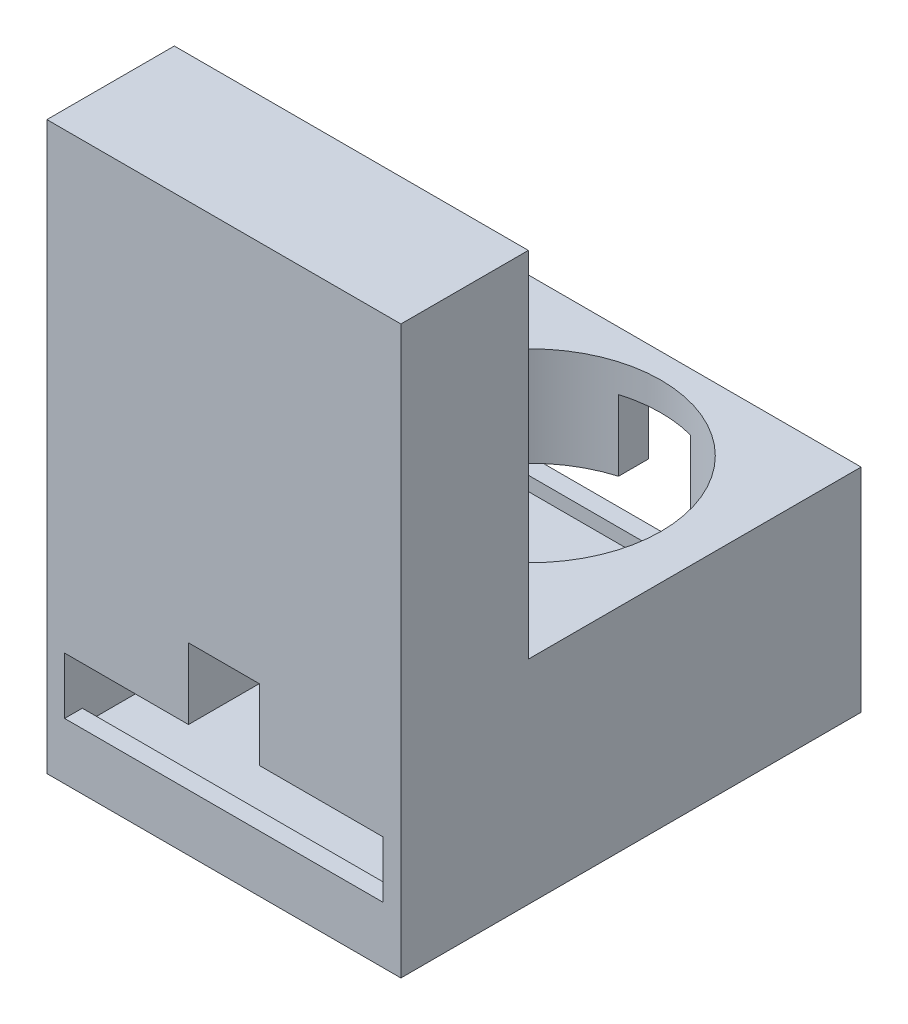
SolidWorks part; units mm, degrees
ref_plane "Front Plane" through (0, 0, 0) normal (0, 0, 1) x (1, 0, 0)
ref_plane "Top Plane" through (0, 0, 0) normal (0, 1, 0) x (1, 0, 0)
ref_plane "Right Plane" through (0, 0, 0) normal (1, 0, 0) x (0, 0, -1)
sketch "Sketch1" plane through (0, 0, 0) normal (0, 1, 0) x (1, 0, 0)
  line L1 (0, 0) -> (50, 0)
  line L2 (0, 0) -> (0, 65)
  line L3 (0, 65) -> (50, 65)
  line L4 (50, 0) -> (50, 65)
  dimension "D1" = 50
  dimension "D2" = 65
extrude "Boss-Extrude1" add sketch "Sketch1" along normal blind 30
sketch "Sketch3" plane through (0, 0, 0) normal (0, 0, 1) x (1, 0, 0)
  line L0 (0, 0) -> (50, 0) construction
  line L1 (2.5, 8) -> (47.5, 8)
  line L2 (2.5, 8) -> (2.5, 16)
  line L3 (2.5, 16) -> (47.5, 16)
  line L4 (47.5, 8) -> (47.5, 16)
  line L5 (25, 16) -> (25, 26) construction
  line L6 (20, 16) -> (30, 16)
  line L7 (20, 16) -> (20, 26)
  line L8 (20, 26) -> (30, 26)
  line L9 (30, 16) -> (30, 26)
  line L11 (25, 0) -> (25, 8) construction
  point P12 (25, 26)
  dimension "D1" = 8
  dimension "D2" = 8
  dimension "D3" = 10
  dimension "D4" = 10
  dimension "D5" = 45
extrude "Cut-Extrude4" cut sketch "Sketch3" against normal through all contours L3 L9 L8 L7 | L1 L4 L3 L2 region at (25, 12, 0) region at (25, 21, 0)
sketch "Sketch4" plane through (47.5, 0, 0) normal (-1, 0, 0) x (0, 0, 1)
  line L0 (-65, 8) -> (0, 8) construction
  line L1 (-62.5, 8) -> (-2.5, 8)
  line L2 (-62.5, 8) -> (-62.5, 6)
  line L3 (-62.5, 6) -> (-2.5, 6)
  line L4 (-2.5, 8) -> (-2.5, 6)
  point P6 (-32.5, 8)
  point P7 (-32.5, 8)
  dimension "D1" = 60
  dimension "D2" = 2
extrude "Cut-Extrude5" cut sketch "Sketch4" along normal up to surface (45 mm away) up to face at (2.5, 12, -32.5)
sketch "Sketch5" plane through (0, 30, 0) normal (0, 1, 0) x (1, 0, 0)
  line L0 (50, 65) -> (0, 65) construction
  circle A0 centre (25.2445, 43) radius 18.5
  point P2 (25.2445, 43.772)
  dimension "D1" = 37
  dimension "D2" = 22
extrude "Cut-Extrude6" cut sketch "Sketch5" against normal up to surface (14 mm away) up to face at (11.25, 16, -32.5)
sketch "Sketch6" plane through (0, 30, 0) normal (0, 1, 0) x (1, 0, 0)
  line L0 (50, 0) -> (50, 65) construction
  line L1 (0, 0) -> (50, 0)
  line L2 (0, 0) -> (0, 18)
  line L3 (0, 18) -> (50, 18)
  line L4 (50, 0) -> (50, 18)
  circle A0 centre (25.2445, 43) radius 18.5 construction
  dimension "D1" = 25
extrude "Boss-Extrude2" add sketch "Sketch6" along normal blind 50
